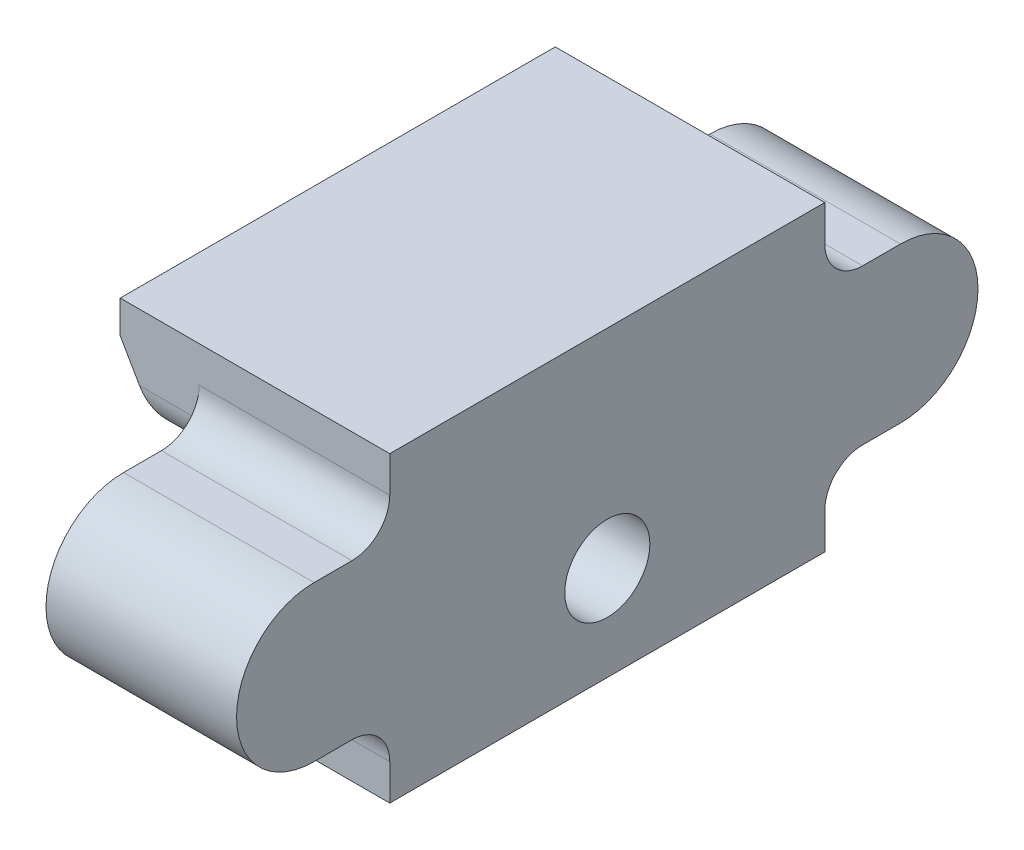
SolidWorks part; units mm, degrees
material "Сплав 2024"
ref_plane "Спереди" through (0, 0, 0) normal (0, 0, 1) x (1, 0, 0)
ref_plane "Сверху" through (0, 0, 0) normal (0, 1, 0) x (1, 0, 0)
ref_plane "Справа" through (0, 0, 0) normal (1, 0, 0) x (0, 0, -1)
sketch "Эскиз1" plane through (0, 0, 0) normal (0, 0, 1) x (1, 0, 0)
  line L1 (0, 0) -> (-10.0746, 0)
  line L2 (-12.0746, 10.5) -> (-15.25, 16)
  line L3 (-15.25, 16) -> (0, 16)
  line L4 (0, 16) -> (0, 0)
  line L5 (-12.0746, 10.5) -> (-10.0746, 10.5)
  line L6 (-10.0746, 10.5) -> (-10.0746, 0)
  dimension "D1" = 2
  dimension "D2" = 5.5
  dimension "D3" = 15.25
  dimension "D4" = 60
  dimension "D6" = 16
extrude "Бобышка-Вытянуть1" add sketch "Эскиз1" along normal blind 23
sketch "Эскиз2" plane through (-10.0746, 0, 0) normal (1, 0, 0) x (0, 0, -1)
  line L0 (-23, 5) -> (0, 5) construction
  line L1 (-23, 0) -> (-23, 16) construction
  line L2 (0, 0) -> (0, 16) construction
  line L3 (-23, 0) -> (0, 0) construction
  line L4 (-19, 0) -> (-19, 16) construction
  line L5 (-23, 16) -> (0, 16) construction
  line L6 (-4, 16) -> (-4, 0) construction
  line L7 (-11.5, 16) -> (-11.5, 0) construction
  circle A0 centre (-19, 5) radius 2.5
  circle A1 centre (-4, 5) radius 2.5
  dimension "D4" = 5
  dimension "D1" = 5
  dimension "D2" = 7.5
extrude "Вырез-Вытянуть1" cut sketch "Эскиз2" along normal blind 4 and the other way through all
hole_wizard "Отверстие с зазором M41" positions "Эскиз4" profile "Эскиз3" hole size "M4" standard "Din" end condition through all
sketch "Эскиз4" plane through (0, 1.5428, 4.5254) normal (-1, 0, 0) x (0, 0, 1)
  line L0 (18.4746, 3.4572) -> (-4.5254, 3.4572) construction
  line L1 (6.9746, 14.4572) -> (6.9746, -1.5428) construction
  point P0 (6.9746, 3.4572)
sketch "Эскиз3" plane through (0, 5, 11.5) normal (0, 1, 0) x (0, 0, -1)
  line L0 (0, 0) -> (0, 15.25)
  line L1 (0, 15.25) -> (2.25, 15.25)
  line L2 (2.25, 15.25) -> (2.25, 0)
  line L5 (2.25, 0) -> (0, 0)
  line L11 (0, -6.35) -> (0, 107.95) construction
  dimension "Диаметр сквозного отверстия" = 4.5
  dimension "Глубина сквозного отверстия" = 15.25
chamfer "Фаска1" distance 1 angle 90 1 edges at (-15.25, 16, 11.5) first distance on face at (-7.625, 16, 11.5)
sketch "Эскиз7" plane through (0, 0, 0) normal (-1, 0, 0) x (0, 0, 1)
  line L0 (23, 8) -> (0, 8) construction
  line L2 (-4, 12.1) -> (0, 12.1)
  line L3 (0, 10.5) -> (0, 0) construction
  line L4 (0, 12.1) -> (0, 3.9)
  line L5 (0, 3.9) -> (-4, 3.9)
  line L6 (11.5, 0) -> (11.5, 9.35) construction
  line L7 (23, 0) -> (0, 0) construction
  line L8 (23, 0) -> (23, 16) construction
  line L9 (23, 12.1) -> (23, 3.9)
  line L10 (27, 12.1) -> (23, 12.1)
  line L11 (23, 3.9) -> (27, 3.9)
  arc A0 (-4, 12.1) -> (-4, 3.9) centre (-4, 8) ccw
  arc A1 (27, 12.1) -> (27, 3.9) centre (27, 8) cw
  point P8 (0, 8)
  dimension "D2" = 4.1
  dimension "D1" = 4
extrude "Бобышка-Вытянуть2" add sketch "Эскиз7" along normal up to surface (10.0746 mm away) up to face at (-10.0746, 7.25, 11.5)
fillet "Скругление1" radius 2 4 edges
fillet "Скругление2" radius 2 2 edges
sketch "Эскиз11" plane through (-10.0746, 0, 0) normal (-1, 0, 0) x (0, 0, 1)
  line L0 (-8.1, 12.8239) -> (-8.1, 1.9255) construction
  line L1 (23, 0) -> (0, 0) construction
  arc A0 (-4, 12.1) -> (-4, 3.9) centre (-4, 8) ccw construction
  point P5 (-8.1, 0)
